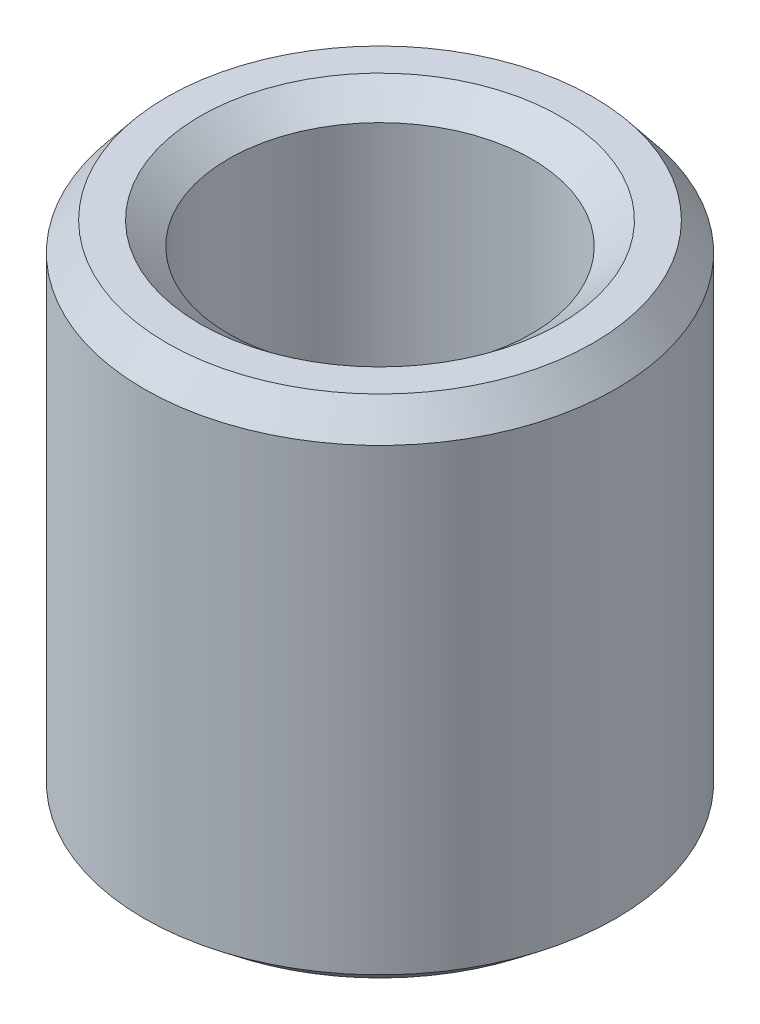
SolidWorks part; units mm, degrees
ref_plane "Front Plane" through (0, 0, 0) normal (0, 0, 1) x (1, 0, 0)
ref_plane "Top Plane" through (0, 0, 0) normal (0, 1, 0) x (1, 0, 0)
ref_plane "Right Plane" through (0, 0, 0) normal (1, 0, 0) x (0, 0, -1)
sketch "Sketch1" plane through (0, 0, 0) normal (0, 1, 0) x (1, 0, 0)
  circle A0 centre (0, 0) radius 20
  dimension "SLEEVE_OD" = 40
extrude "Boss-Extrude1" add sketch "Sketch1" along normal blind 43.2094
sketch "Sketch2" plane through (0, 0, 0) normal (0, 1, 0) x (1, 0, 0)
  circle A0 centre (0, 0) radius 12.8457
  dimension "BORE_D" = 25.6915
extrude "Cut-Extrude1" cut sketch "Sketch2" along normal through all
chamfer "Chamfer1" distance 2.408 angle 38.748 4 edges at (0, 43.2094, 12.8457) (0, 0, 12.8457) (0, 0, 20) (0, 43.2094, 20) first distance on face at (0, 43.2094, 12.8457) first distance on face at (0, 0, 12.8457) first distance on face at (0, 43.2094, 20)
